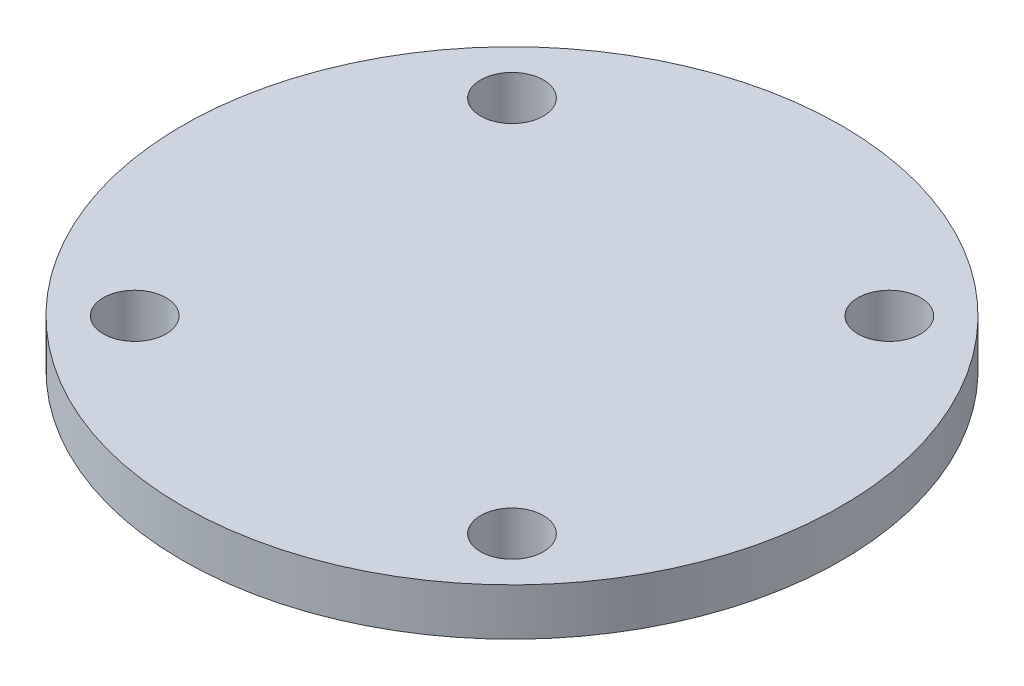
SolidWorks part; units mm, degrees
ref_plane "Front Plane" through (0, 0, 0) normal (0, 0, 1) x (1, 0, 0)
ref_plane "Top Plane" through (0, 0, 0) normal (0, 1, 0) x (1, 0, 0)
ref_plane "Right Plane" through (0, 0, 0) normal (1, 0, 0) x (0, 0, -1)
sketch "Sketch1" plane through (0, 0, 0) normal (0, 1, 0) x (1, 0, 0)
  circle A0 centre (0, 0) radius 17 construction
  circle A1 centre (0, 0) radius 12
  circle A2 centre (0, 0) radius 21
  circle A3 centre (-12.0208, 12.0208) radius 2
  circle A4 centre (12.0208, 12.0208) radius 2
  circle A5 centre (12.0208, -12.0208) radius 2
  circle A6 centre (-12.0208, -12.0208) radius 2
  dimension "D2" = 4
extrude "Boss-Extrude1" add sketch "Sketch1" along normal blind 3
extrude "Boss-Extrude2" add sketch "Sketch1<2>" against normal blind 1 and the other way blind 3 contours A1 region at (0, 0, 0)
sketch "Sketch1<2>" plane through (0, 0, 0) normal (0, 1, 0) x (1, 0, 0) same geometry as "Sketch1"
